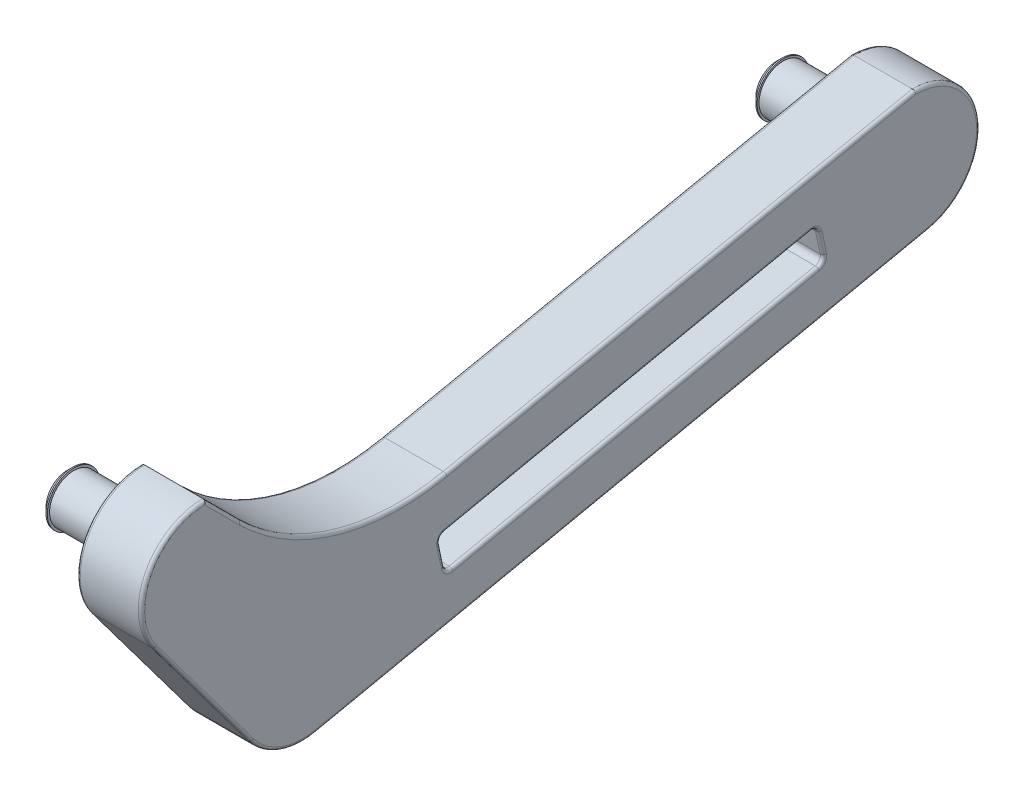
SolidWorks part; units mm, degrees
ref_plane "前视基准面" through (0, 0, 0) normal (0, 0, 1) x (1, 0, 0)
ref_plane "上视基准面" through (0, 0, 0) normal (0, 1, 0) x (1, 0, 0)
ref_plane "右视基准面" through (0, 0, 0) normal (1, 0, 0) x (0, 0, -1)
other "Configuration Table"
sketch "草图1" plane through (0, 0, 0) normal (1, 0, 0) x (0, 0, -1)
  line L0 (0, 0) -> (110, 0) construction
  line L1 (0, 10) -> (110, 10)
  line L2 (0, -10) -> (110, -10)
  arc A0 (0, 10) -> (0, -10) centre (0, 0) ccw
  arc A1 (110, -10) -> (110, 10) centre (110, 0) ccw
  circle A2 centre (0, 0) radius 3.75
  circle A3 centre (110, 0) radius 3.75
  point P3 (55, 0)
  dimension "D2" = 10
  dimension "D3" = 7.5
  dimension "D4" = 7.5
  dimension "D1" = 110
extrude "凸台-拉伸1" add sketch "草图1" along normal blind 10 contours A2 | L2 A1 L1 A0
sketch "草图2" plane through (10, 0, 0) normal (1, 0, 0) x (0, 0, -1)
  circle A0 centre (0, 0) radius 3.75 construction
  circle A1 centre (0, 0) radius 3.75
  circle A2 centre (110, 0) radius 3.75 construction
  circle A3 centre (110, 0) radius 3.75
extrude "凸台-拉伸2" add sketch "草图2" against normal blind 20.5
sketch "草图3" plane through (0, 0, 0) normal (-1, 0, 0) x (0, 0, 1)
  line L0 (0, 0) -> (-15, 0) construction
  line L1 (8, -6) -> (-7, -26)
  line L2 (0, 10) -> (-110, 10)
  line L3 (-110, -10) -> (0, -10)
  line L4 (0, 10) -> (-110, 10)
  line L6 (-17.0601, -29.7855) -> (-112.0601, -9.7855)
  line L7 (-15, 0) -> (-15, -20) construction
  arc A0 (-17.0601, -29.7855) -> (-7, -26) centre (-15, -20) ccw
  arc A2 (0, -10) -> (0, 10) centre (0, 0) ccw
  arc A3 (-110, 10) -> (-110, -10) centre (-110, 0) ccw
  arc A4 (8, -6) -> (0, 10) centre (0, 0) ccw
  arc A5 (-110, 10) -> (-112.0601, -9.7855) centre (-110, 0) ccw
  dimension "D2" = 10
  dimension "D3" = 15
  dimension "D4" = 20
  dimension "D1" = 0
extrude "凸台-拉伸3" add sketch "草图3" against normal blind 10
sketch "草图4" plane through (0, 0, 0) normal (-1, 0, 0) x (0, 0, 1)
  line L0 (0, 0) -> (-110, 0) construction
  line L1 (0, 10) -> (-5.4706, 4.5294)
  line L3 (-7, -26) -> (8, -6)
  line L4 (0, 10) -> (-110, 10)
  line L5 (-112.0601, -9.7855) -> (-17.0601, -29.7855)
  line L7 (0, 10) -> (-110, 10)
  line L9 (-37.291, -5) -> (-110, 10)
  arc A0 (-37.291, -5) -> (-5.4706, 4.5294) centre (-30.2193, 29.2782) ccw
  arc A3 (8, -6) -> (0, 10) centre (0, 0) ccw
  arc A4 (-110, 10) -> (-112.0601, -9.7855) centre (-110, 0) ccw
  arc A5 (-17.0601, -29.7855) -> (-7, -26) centre (-15, -20) ccw
  point P7 (-5.2413, 4.7587)
  point P12 (-38.5329, -5.7067)
  point P13 (-45, 0)
  point P14 (-5.2413, 4.7587)
  point P16 (-10, 0)
  point P17 (-4.1421, 5.7897)
  dimension "D4" = 35
  dimension "D2" = 45
  dimension "D3" = 15
  dimension "D1" = 0
extrude "切除-拉伸1" cut sketch "草图4" against normal through all
sketch "草图5" plane through (10, 0, 0) normal (1, 0, 0) x (0, 0, -1)
  line L4 (37.2268, -18.3864) -> (36.0937, -13.0044)
  line L5 (36.0937, -13.0044) -> (94.8067, -0.6438)
  line L6 (94.8067, -0.6438) -> (95.9398, -6.0258)
  line L7 (95.9398, -6.0258) -> (37.2268, -18.3864)
  line L8 (112.0601, -9.7855) -> (107.9824, 9.5838) construction
  line L9 (110, 10) -> (37.291, -5) construction
  line L10 (112.0601, -9.7855) -> (17.0601, -29.7855) construction
  dimension "D1" = 15
  dimension "D2" = 7
  dimension "D3" = 60
  dimension "D4" = 5.5
extrude "切除-拉伸2" cut sketch "草图5" against normal blind 10
fillet "圆角1" radius 1 4 edges at (5, -18.3864, -37.2268) (5, -6.0258, -95.9398) (5, -0.6438, -94.8067) (5, -13.0044, -36.0937)
sketch "草图6" plane through (-10.5, 0, 0) normal (-1, 0, 0) x (0, 0, 1)
  circle A0 centre (0, 0) radius 4.1
  dimension "D1" = 8.2
extrude "凸台-拉伸4" add sketch "草图6" along normal blind 1
chamfer "倒角1" distance 0.8 angle 45 1 edges at (-11.5, 0, 4.1)
sketch "草图7" plane through (-10.5, 0, 0) normal (-1, 0, 0) x (0, 0, 1)
  circle A2 centre (-110, 0) radius 4.05
  circle A3 centre (-110, 0) radius 3.75 construction
  circle A4 centre (-110, 0) radius 3.75 construction
  dimension "D1" = 8.1
extrude "凸台-拉伸5" add sketch "草图7" along normal blind 1
chamfer "倒角2" distance 0.8 angle 45 1 edges at (-11.5, 0, -105.95)
fillet "圆角2" radius 0.5 34 edges at (10, -4.2506, -20.1783) (10, 2.5, -73.6455) (10, 1.0356, -119.9462) (10, -19.7855, -64.5601) (10, -29.3593, -11.4782) (10, -16, 0.5) (10, 4.4721, 8.9443) (10, 7.2647, -2.7353) (10, -5.7995, -95.5928) (10, -3.3348, -95.3733) (10, -0.9907, -94.5805) (10, -6.8241, -65.4502) (10, -13.2307, -36.4407) (10, -15.6954, -36.6603) (10, -18.0395, -37.4531) (10, -12.2061, -66.5833) (0, 0, -3.75) (0, 0, -113.75) (0, -16, 0.5) (0, -29.3593, -11.4782) (0, -19.7855, -64.5601) (0, 1.0356, -119.9462) (0, 2.5, -73.6455) (0, -4.2506, -20.1783) (0, 7.2647, -2.7353) (0, 4.4721, 8.9443) (0, -0.9907, -94.5805) (0, -3.3348, -95.3733) (0, -5.7995, -95.5928) (0, -12.2061, -66.5833) (0, -18.0395, -37.4531) (0, -15.6954, -36.6603) (0, -13.2307, -36.4407) (0, -6.8241, -65.4502)
